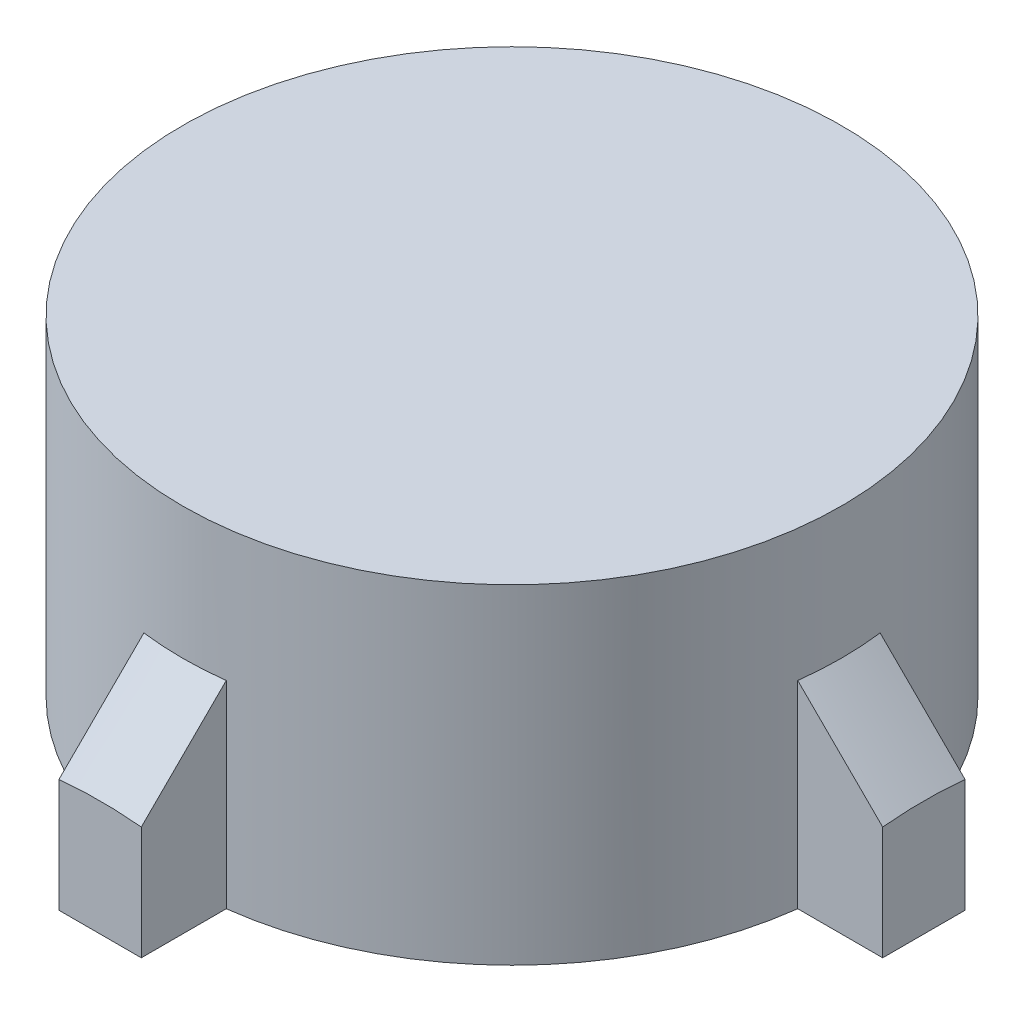
SolidWorks part; units mm, degrees
ref_plane "Front Plane" through (0, 0, 0) normal (0, 0, 1) x (1, 0, 0)
ref_plane "Top Plane" through (0, 0, 0) normal (0, 1, 0) x (1, 0, 0)
ref_plane "Right Plane" through (0, 0, 0) normal (1, 0, 0) x (0, 0, -1)
sketch "Sketch1" plane through (0, 0, 0) normal (0, 1, 0) x (1, 0, 0)
  circle A0 centre (0, 0) radius 100
  dimension "D1" = 200
extrude "Boss-Extrude1" add sketch "Sketch1" along normal blind 100
sketch "Sketch2" plane through (0, 0, 0) normal (0, -1, 0) x (1, 0, 0)
  line L1 (-125, -12.5) -> (125, -12.5)
  line L2 (-125, -12.5) -> (-125, 12.5)
  line L3 (-125, 12.5) -> (125, 12.5)
  line L4 (125, -12.5) -> (125, 12.5)
  line L5 (-125, -12.5) -> (125, 12.5) construction
  line L6 (-125, 12.5) -> (125, -12.5) construction
  line L7 (-12.5, -125) -> (12.5, -125)
  line L8 (-12.5, -125) -> (-12.5, 125)
  line L9 (-12.5, 125) -> (12.5, 125)
  line L10 (12.5, -125) -> (12.5, 125)
  line L11 (-12.5, -125) -> (12.5, 125) construction
  line L12 (-12.5, 125) -> (12.5, -125) construction
  point P0 (0, 0)
  point P5 (0, 0)
  circle M5 centre (0, 0) radius 100
  dimension "D1" = 25
  dimension "D2" = 250
extrude "Boss-Extrude2" add sketch "Sketch2" against normal blind 10 contours L3 L2 L1 M5 | L1 L4 L3 M5 | L10 L9 L8 M5 | L7 L10 L8 M5 region at (-112.3684, 0, 0) region at (0, 0, -112.3684) region at (0, 0, 112.3684) region at (112.3684, 0, 0)
chamfer "Chamfer1" distance 50 angle 45 4 edges at (0, 10, -100) (100, 10, 0) (0, 10, 100) (-100, 10, 0)
